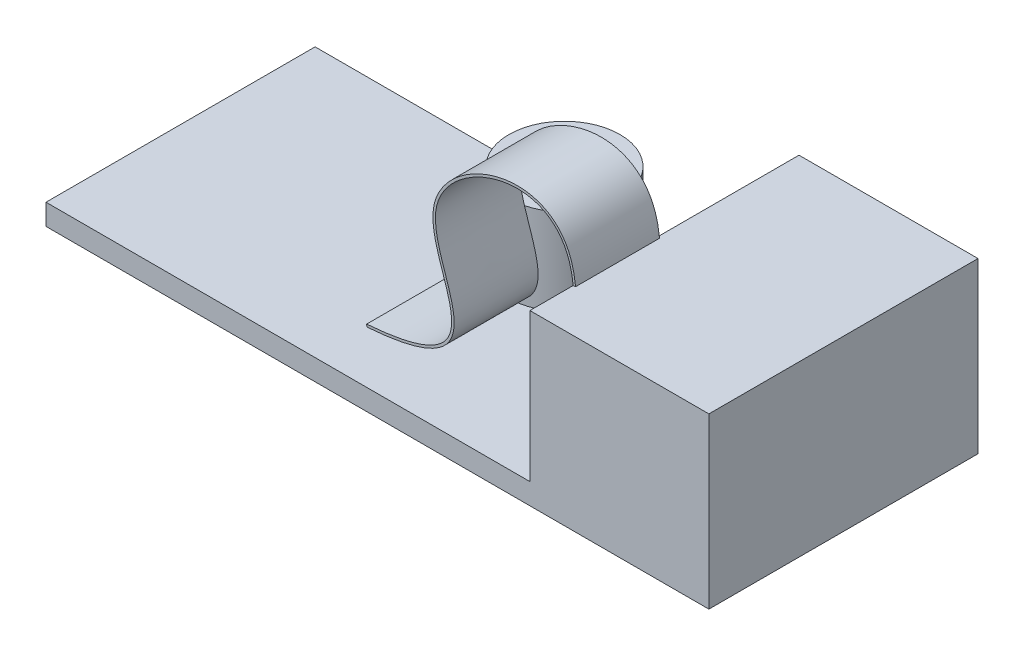
SolidWorks part; units mm, degrees
ref_plane "Front Plane" through (0, 0, 0) normal (0, 0, 1) x (1, 0, 0)
ref_plane "Top Plane" through (0, 0, 0) normal (0, 1, 0) x (1, 0, 0)
ref_plane "Right Plane" through (0, 0, 0) normal (1, 0, 0) x (0, 0, -1)
sketch "Sketch1" plane through (0, 0, 0) normal (0, 1, 0) x (1, 0, 0)
  line L1 (0, 0) -> (53.7, 0)
  line L2 (0, 0) -> (0, 21.8)
  line L3 (0, 21.8) -> (53.7, 21.8)
  line L4 (53.7, 0) -> (53.7, 21.8)
  dimension "D1" = 21.8
  dimension "D2" = 53.7
extrude "Boss-Extrude1" add sketch "Sketch1" along normal blind 1.7
sketch "Sketch2" plane through (0, 1.7, 0) normal (0, 1, 0) x (1, 0, 0)
  line L0 (53.7, 0) -> (53.7, 21.8) construction
  line L1 (53.7, 21.8) -> (39.2, 21.8)
  line L2 (53.7, 21.8) -> (53.7, 0)
  line L3 (53.7, 0) -> (39.2, 0)
  line L4 (39.2, 21.8) -> (39.2, 0)
  line L5 (53.7, 21.8) -> (0, 21.8) construction
  line L6 (0, 0) -> (53.7, 0) construction
  dimension "D1" = 14.5
extrude "Boss-Extrude2" add sketch "Sketch2" along normal blind 12
ref_plane "Plane1" through (0, 0, -3.5) normal (0, 0, 1) x (1, 0, 0)
sketch "Sketch3" plane through (0, 0, -3.5) normal (0, 0, 1) x (1, 0, 0)
  line L0 (39.2, 13.7) -> (39.3991, 13.7189)
  line L1 (22.4909, 2.4396) -> (22.4759, 2.639)
  spline S0 degree 3 poles (39.2, 13.7) (38.4876, 21.2039) (19.6659, 15.1064) (34.7036, 3.3582) (22.4909, 2.4396) knots 0 0 0 0 0.499649 1 1 1 1
  spline S1 degree 1 poles (39.3991, 13.7189) (22.4759, 2.639) knots 0 0 1 1 construction
  spline S2 degree 3 poles (39.3991, 13.7189) (39.3772, 13.95) (39.3129, 14.4227) (39.1212, 15.2576) (38.7629, 16.1688) (38.1682, 17.0369) (37.1899, 17.9105) (35.6995, 18.4872) (33.7199, 18.4782) (31.745, 17.8948) (29.3773, 16.5029) (27.7807, 14.3641) (27.8427, 11.9326) (28.3578, 10.1113) (28.9943, 8.3322) (29.4222, 6.6748) (29.3309, 5.2542) (28.6144, 4.2775) (27.4396, 3.6064) (26.2132, 3.1816) (24.8602, 2.9036) (23.5831, 2.7348) (22.8364, 2.6661) (22.4759, 2.639) knots 0 0 0 0 0.015625 0.03125 0.0625 0.09375 0.125 0.1875 0.25 0.3125 0.375 0.5 0.5625 0.625 0.6875 0.75 0.8125 0.875 0.90625 0.9375 0.96875 0.984375 1 1 1 1
  dimension "D1" = 0.2
extrude "Boss-Extrude3" add sketch "Sketch3" against normal blind 6.8 separate body
sketch "Sketch4" plane through (0, 1.7, 0) normal (0, 1, 0) x (1, 0, 0)
  line L0 (25.5, 21) -> (32.3048, 21) construction
  line L1 (0, 0) -> (39.2, 0) construction
  line L2 (30, 16.5) -> (30, 30.3879) construction
  line L3 (0, 21.8) -> (0, 0) construction
  circle A0 centre (25.5, 16.5) radius 4.5
  dimension "D1" = 9
  dimension "D2" = 21
  dimension "D3" = 30
extrude "Boss-Extrude4" add sketch "Sketch4" along normal blind 7
